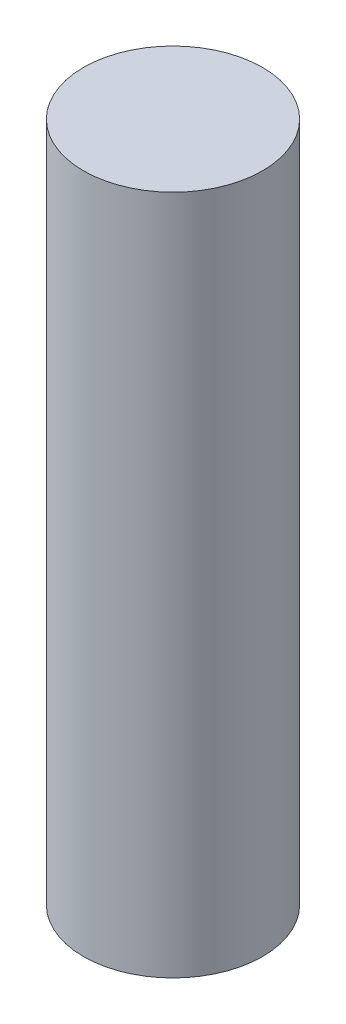
SolidWorks part; units mm, degrees
ref_plane "Front Plane" through (0, 0, 0) normal (0, 0, 1) x (1, 0, 0)
ref_plane "Top Plane" through (0, 0, 0) normal (0, 1, 0) x (1, 0, 0)
ref_plane "Right Plane" through (0, 0, 0) normal (1, 0, 0) x (0, 0, -1)
sketch "Sketch1" plane through (0, 0, 0) normal (0, 1, 0) x (1, 0, 0)
  circle A0 centre (0, 0) radius 5
  dimension "D1" = 10
extrude "Boss-Extrude1" add sketch "Sketch1" along normal blind 19 and the other way blind 19
